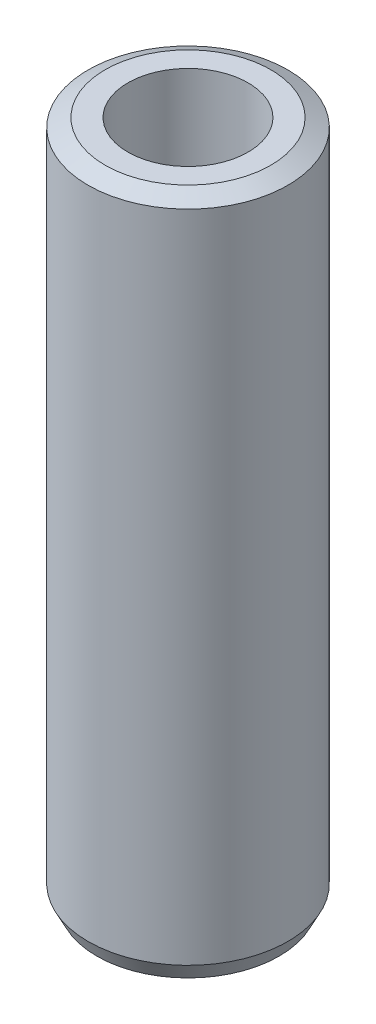
SolidWorks part; units mm, degrees
ref_plane "Front Plane" through (0, 0, 0) normal (0, 0, 1) x (1, 0, 0)
ref_plane "Top Plane" through (0, 0, 0) normal (0, 1, 0) x (1, 0, 0)
ref_plane "Right Plane" through (0, 0, 0) normal (1, 0, 0) x (0, 0, -1)
sketch "Sketch1" plane through (0, 0, 0) normal (0, 1, 0) x (1, 0, 0)
  circle A0 centre (0, 0) radius 42.5
  dimension "SHAFT_OD" = 85
extrude "Boss-Extrude1" add sketch "Sketch1" along normal blind 289.5237
sketch "Sketch2" plane through (0, 0, 0) normal (0, 1, 0) x (1, 0, 0)
  circle A0 centre (0, 0) radius 25.5556
  dimension "BORE_D" = 51.1113
extrude "Cut-Extrude1" cut sketch "Sketch2" along normal through all
chamfer "Chamfer1" distance 3.7184 angle 62.936 2 edges at (0, 289.5237, 42.5) (0, 0, 42.5) first distance on face at (0, 289.5237, 42.5) first distance on face at (0, 0, 25.5556)
